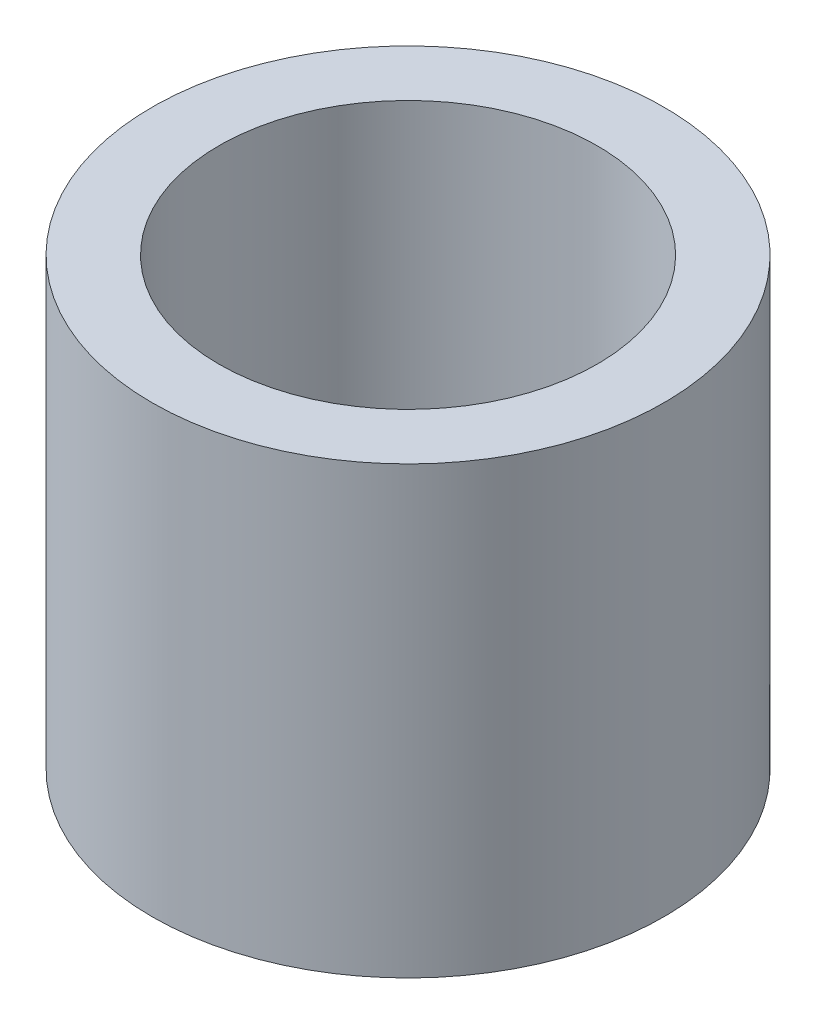
SolidWorks part; units mm, degrees
ref_plane "Спереди" through (0, 0, 0) normal (0, 0, 1) x (1, 0, 0)
ref_plane "Сверху" through (0, 0, 0) normal (0, 1, 0) x (1, 0, 0)
ref_plane "Справа" through (0, 0, 0) normal (1, 0, 0) x (0, 0, -1)
sketch "Эскиз1" plane through (0, 0, 0) normal (0, 1, 0) x (1, 0, 0)
  circle A0 centre (0, 0) radius 23
  dimension "D1" = 46
extrude "Бобышка-Вытянуть1" add sketch "Эскиз1" along normal blind 10
sketch "Эскиз2" plane through (0, 10, 0) normal (0, 1, 0) x (1, 0, 0)
  circle A0 centre (0, 0) radius 23
  circle A1 centre (0, 0) radius 17
  circle A2 centre (0, 0) radius 23 construction
  dimension "D1" = 34
  dimension "D2" = 0
extrude "Бобышка-Вытянуть2" add sketch "Эскиз2" along normal blind 30
